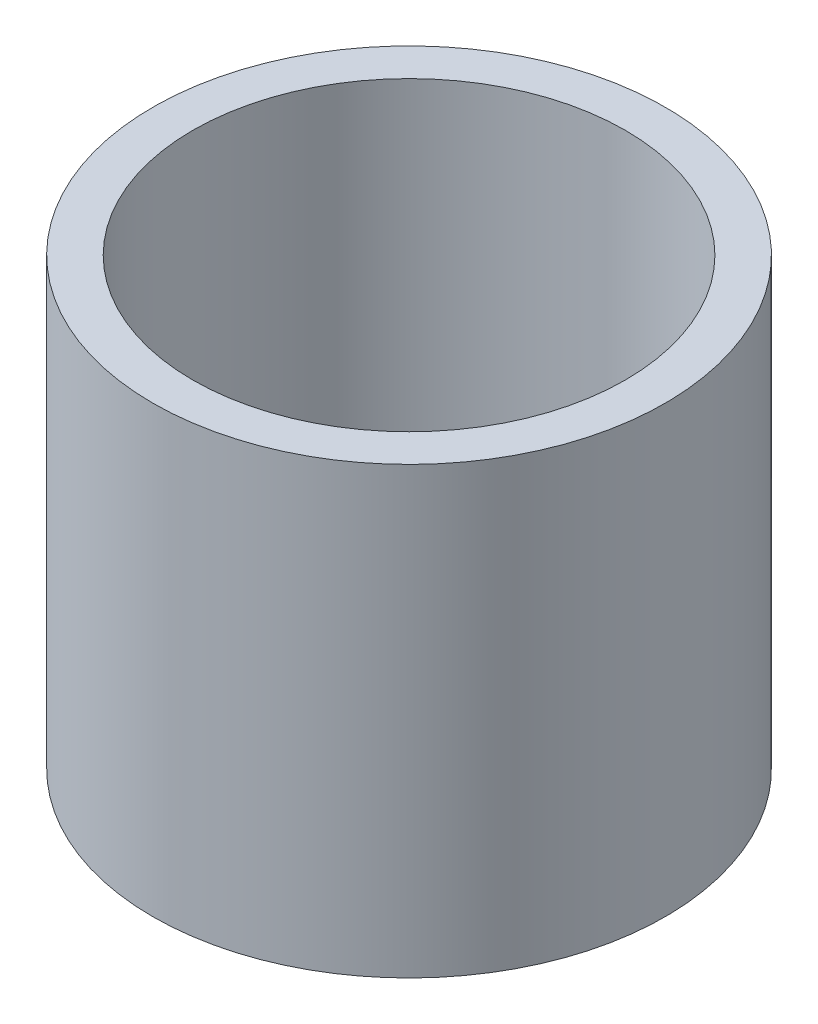
SolidWorks part; units mm, degrees
ref_plane "Front Plane" through (0, 0, 0) normal (0, 0, 1) x (1, 0, 0)
ref_plane "Top Plane" through (0, 0, 0) normal (0, 1, 0) x (1, 0, 0)
ref_plane "Right Plane" through (0, 0, 0) normal (1, 0, 0) x (0, 0, -1)
sketch "Sketch1" plane through (0, 0, 0) normal (0, 1, 0) x (1, 0, 0)
  circle A0 centre (0, 0) radius 27.5
  dimension "SLEEVE_OD" = 55
extrude "Boss-Extrude1" add sketch "Sketch1" along normal blind 47.7284
sketch "Sketch2" plane through (0, 0, 0) normal (0, 1, 0) x (1, 0, 0)
  circle A0 centre (0, 0) radius 23.2089
  dimension "BORE_D" = 46.4178
extrude "Cut-Extrude1" cut sketch "Sketch2" along normal through all
chamfer "Chamfer1" distance 2.7532 angle 30 rebuild error yes
